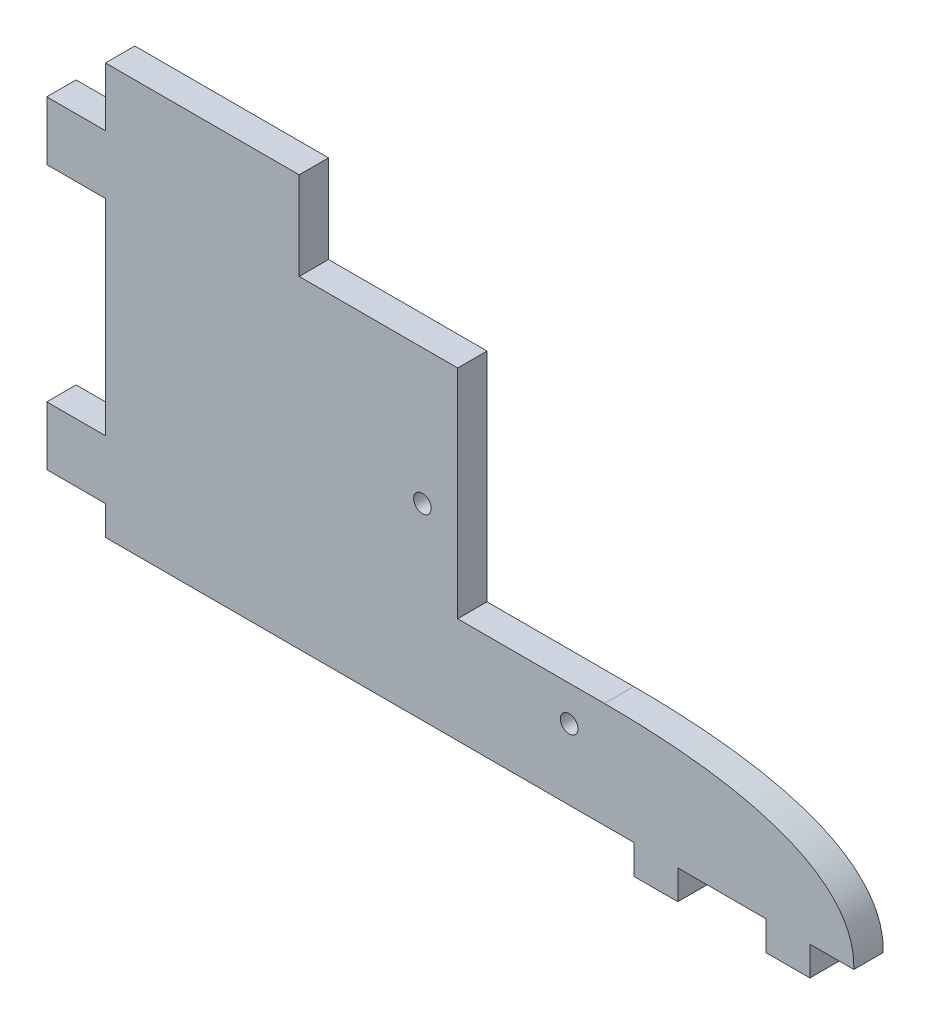
SolidWorks part; units mm, degrees
ref_plane "Plan de face" through (0, 0, 0) normal (0, 0, 1) x (1, 0, 0)
ref_plane "Plan de dessus" through (0, 0, 0) normal (0, 1, 0) x (1, 0, 0)
ref_plane "Plan de droite" through (0, 0, 0) normal (1, 0, 0) x (0, 0, -1)
sketch "Esquisse1" plane through (0, 0, 0) normal (0, 0, 1) x (1, 0, 0)
  line L1 (0, 0) -> (37, 0)
  line L2 (0, 0) -> (0, 55)
  line L3 (0, 55) -> (12, 55)
  line L4 (37, 0) -> (37, 18)
  line L6 (12, 55) -> (12, 18)
  line L7 (12, 18) -> (37, 18)
  circle A0 centre (6, 32) radius 1.5
  circle A1 centre (31, 12) radius 1.5
  dimension "D3" = 20
  dimension "D4" = 3
  dimension "D1" = 6
  dimension "D2" = 55
  dimension "D5" = 12
  dimension "D7" = 25
  dimension "D8" = 6
  dimension "D9" = 6
extrude "Boss.-Extru.1" add sketch "Esquisse1" along normal blind 5
sketch "Esquisse2" plane through (0, 0, 5) normal (0, 0, 1) x (1, 0, 0)
  line L0 (37, 18) -> (12, 18) construction
  line L1 (37, 0) -> (42, 0)
  line L2 (37, 0) -> (37, 18)
  line L3 (49.5, 0) -> (64.5, 0)
  line L4 (12, 55) -> (0, 55) construction
  line L5 (72, 0) -> (72, -5)
  line L6 (72, -5) -> (64.5, -5)
  line L7 (64.5, 0) -> (64.5, -5)
  line L8 (72, 0) -> (79.5, 0)
  line L9 (49.5, 0) -> (49.5, -5)
  line L10 (49.5, -5) -> (42, -5)
  line L11 (42, 0) -> (42, -5)
  line L12 (0, 0) -> (-48, 0)
  line L13 (0, 0) -> (0, 55)
  line L14 (0, 55) -> (-15, 55)
  line L15 (-48, 60) -> (-48, 70)
  line L16 (-48, 5) -> (-58, 5)
  line L17 (-48, 15) -> (-48, 50)
  line L18 (-15, 55) -> (-15, 70)
  line L19 (-48, 15) -> (-58, 15)
  line L20 (-48, 0) -> (-48, 5)
  line L21 (-58, 5) -> (-58, 15)
  line L22 (-48, 60) -> (-58, 60)
  line L24 (-48, 50) -> (-58, 50)
  line L25 (-58, 60) -> (-58, 50)
  line L36 (-48, 70) -> (-15, 70)
  spline S0 degree 3 poles (37, 18) (79.2395, 18) (79.5, 3.8743) (79.5, 0) knots 0 0 0 0 1 1 1 1
  dimension "D1" = 42.5
  dimension "D2" = 7.5
  dimension "D3" = 5
  dimension "D4" = 5
  dimension "D5" = 15
  dimension "D6" = 15
  dimension "D7" = 70
  dimension "D8" = 10
  dimension "D9" = 5
  dimension "D10" = 35
  dimension "D11" = 10
  dimension "D12" = 48
extrude "Boss.-Extru.2" add sketch "Esquisse2" against normal blind 5
